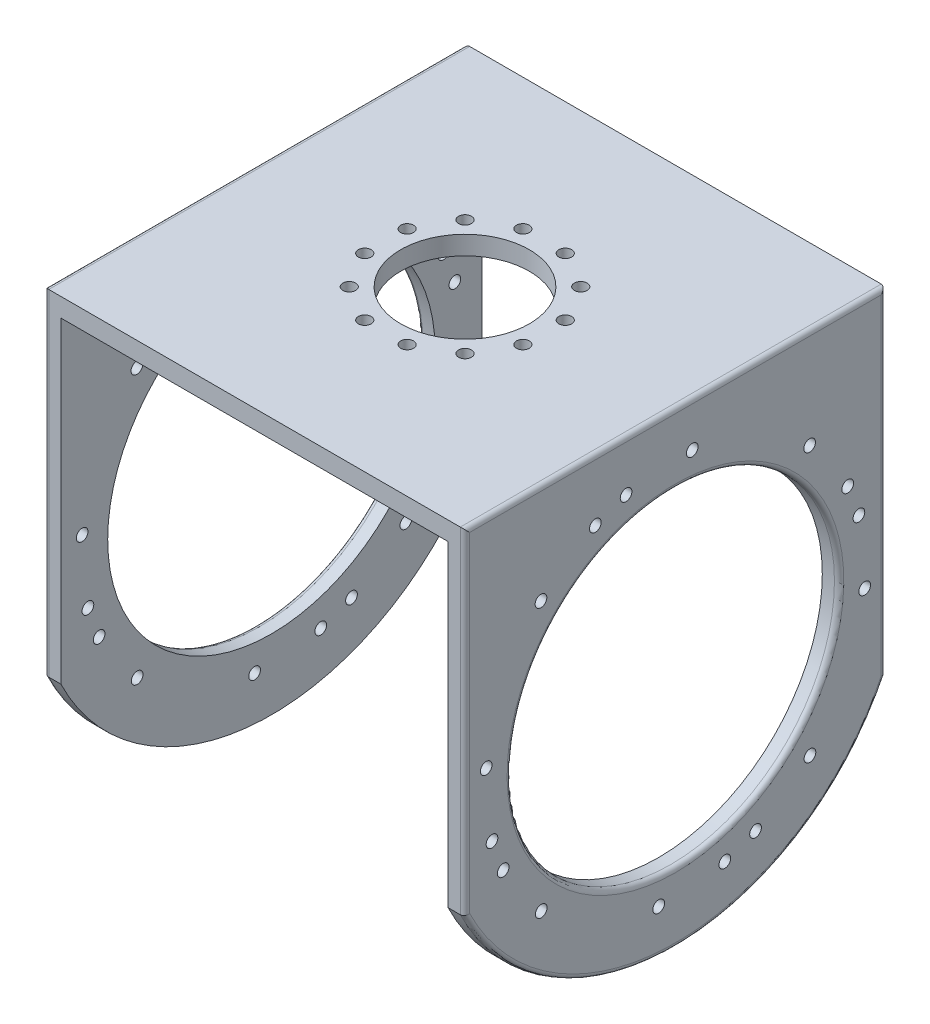
SolidWorks part; units mm, degrees
material "6061 合金"
ref_plane "前视基准面" through (0, 0, 0) normal (0, 0, 1) x (1, 0, 0)
ref_plane "上视基准面" through (0, 0, 0) normal (0, 1, 0) x (1, 0, 0)
ref_plane "右视基准面" through (0, 0, 0) normal (1, 0, 0) x (0, 0, -1)
other "Configuration Table"
sketch "草图1" plane through (0, 0, 0) normal (0, 0, 1) x (1, 0, 0)
  line L0 (0, 0) -> (0, 218.3382) construction
  line L1 (-90, 200) -> (90, 200)
  line L2 (90, 200) -> (90, 0)
  line L3 (90, 0) -> (82.8, 0)
  line L4 (82.8, 0) -> (82.8, 192)
  line L5 (82.8, 192) -> (-82.8, 192)
  line L6 (-82.8, 0) -> (-82.8, 192)
  line L7 (-90, 0) -> (-82.8, 0)
  line L8 (-90, 200) -> (-90, 0)
  point P11 (0, 192)
  point P14 (0, 200)
  dimension "D1" = 8
  dimension "D2" = 7.2
  dimension "D3" = 200
  dimension "D4" = 90
extrude "凸台-拉伸1" add sketch "草图1" along normal blind 180
sketch "草图2" plane through (0, 200, 0) normal (0, 1, 0) x (1, 0, 0)
  line L0 (-107.1953, -90) -> (124.7074, -90) construction
  line L1 (0, 14.5236) -> (0, -191.0225) construction
  line L2 (90, 0) -> (-90, 0) construction
  line L3 (90, -180) -> (-90, -180) construction
  circle A0 centre (0, -90) radius 27.5
  dimension "D1" = 55
extrude "切除-拉伸1" cut sketch "草图2" against normal blind 180
sketch "草图3" plane through (90, 0, 0) normal (1, 0, 0) x (0, 0, -1)
  line L0 (-202.0275, 100) -> (22.0275, 100) construction
  line L1 (-90, 182.9754) -> (-90, -6.0566) construction
  line L2 (-180, 0) -> (0, 0) construction
  line L3 (-180, 200) -> (0, 200) construction
  line L4 (0, 0) -> (0, 200) construction
  line L5 (-180, 0) -> (-180, 200) construction
  circle A0 centre (-90, 100) radius 70
  dimension "D1" = 140
extrude "切除-拉伸2" cut sketch "草图3" against normal blind 217 contours A0
sketch "草图4" plane through (0, 0, 0) normal (1, 0, 0) x (0, 0, -1)
  line L0 (-90, 200) -> (-90, 143.0513) construction
  line L1 (-62.5, 200) -> (-117.5, 200) construction
  line L2 (-70, 430) -> (60, 66.6573)
  line L3 (60, 66.6573) -> (-90, 66.6573) construction
  line L4 (-90, 66.6573) -> (-90, 700) construction
  line L5 (-70, 700) -> (60, 700)
  line L6 (60, 700) -> (60, 66.6573)
  line L7 (-70, 700) -> (-70, 430)
  circle A0 centre (-90, 100) radius 70 construction
  dimension "D1" = 500
  dimension "D2" = 130
  dimension "D3" = 150
  dimension "D4" = 230
  dimension "D5" = 20
revolve "切除-旋转6" [suppressed] cut sketch "草图4" angle 360 about L4
sketch "草图6" [suppressed] plane through (0, 0, 0) normal (1, 0, 0) x (0, 0, -1)
  line L0 (15.1538, 192) -> (60, 66.6573)
  line L1 (-25.1812, 192) -> (0, 192) construction
  line L2 (60, 66.6573) -> (-90, 66.6573) construction
  line L3 (60, 66.6573) -> (51.5034, 66.6573)
  line L4 (51.5034, 66.6573) -> (6.6571, 192)
  line L5 (-70, 430) -> (60, 66.6573) construction
  line L6 (6.6571, 192) -> (15.1538, 192)
  line L7 (-90, 66.6573) -> (-90, 200) construction
  dimension "D1" = 8
revolve "旋转1" [suppressed] add sketch "草图6" angle 360 about L7
sketch "草图7" [suppressed] plane through (0, 0, 0) normal (0, 0, 1) x (1, 0, 0)
  line L0 (90, 0) -> (90, 200)
  line L1 (90, 200) -> (162.5084, 200)
  line L2 (162.5084, 200) -> (162.5084, -21.519)
  line L3 (162.5084, -21.519) -> (-191.6551, -21.519)
  line L4 (-191.6551, -21.519) -> (-191.6551, 200)
  line L5 (-191.6551, 200) -> (-90, 200)
  line L6 (-90, 200) -> (-90, 0)
  line L7 (-90, 0) -> (-82.8, 0)
  line L10 (-35.2505, 192) -> (35.2505, 192)
  line L12 (82.8, 0) -> (90, 0)
  line L14 (35.2505, 192) -> (-35.2505, 192) construction
  line L15 (82.8, 0) -> (82.8, 120.3462)
  line L16 (82.8, 120.3462) -> (35.2505, 192)
  line L17 (-82.8, 0) -> (-82.8, 120.3462)
  line L18 (-82.8, 120.3462) -> (-35.2505, 192)
  line L19 (0, 0) -> (0, 120.3462) construction
  line L21 (35.2505, 192) -> (82.8, 192) construction
  line L22 (-82.8, 0) -> (-82.8, 120.3462) construction
  line L23 (-141.5034, 66.6573) -> (141.5034, 66.6573) construction
  line L24 (-35.2505, 192) -> (35.2505, 192) construction
  dimension "D1" = 53.6889
  dimension "D2" = 35.2505
extrude "切除-拉伸3" [suppressed] cut sketch "草图7" against normal through all both and the other way through all
sketch "草图8" [suppressed] plane through (-90, 0, 0) normal (-1, 0, 0) x (0, 0, 1)
  line L0 (0, 0) -> (0, 200)
  line L1 (0, 200) -> (180, 200)
  line L2 (180, 200) -> (180, 0)
  line L3 (180, 106.4129) -> (180, 0) construction
  line L4 (180, 0) -> (231.7354, 0)
  line L5 (231.7354, 0) -> (231.7354, 213.4055)
  line L6 (231.7354, 213.4055) -> (-43.5189, 213.4055)
  line L7 (-43.5189, 213.4055) -> (-43.5189, 0)
  line L8 (-43.5189, 0) -> (0, 0)
extrude "切除-拉伸4" [suppressed] cut sketch "草图8" against normal through all both
sketch "草图9" plane through (90, 0, 0) normal (1, 0, 0) x (0, 0, -1)
  line L3 (0, 56.411) -> (0, 0)
  line L4 (-180, 200) -> (-180, 0)
  line L5 (-180, 0) -> (0, 0)
  line L6 (0, 0) -> (0, 200)
  line L7 (0, 200) -> (-180, 200)
  line L8 (-180, 56.411) -> (-180, 0)
  line L9 (-180, 0) -> (0, 0)
  line L11 (0, 200) -> (-180, 200) construction
  circle A0 centre (-90, 100) radius 70 construction
  circle A1 centre (-90, 100) radius 70 construction
  arc A3 (-180, 56.411) -> (0, 56.411) centre (-90, 100) ccw
  line M11 (-180, 200) -> (-180, 0)
  line M12 (-180, 0) -> (0, 0)
  line M13 (0, 0) -> (0, 200)
  dimension "D1" = 0
extrude "切除-拉伸5" cut sketch "草图9" against normal through all both contours A3 L9 M13 | A3 M11 M12 region at (90, 15.6044, 21.0435) region at (90, 15.6044, 158.9565)
fillet "圆角1" [suppressed] radius 2
fillet "圆角2" radius 2 10 edges at (90, 200, 90) (90, 128.2055, 0) (90, 0, 90) (90, 128.2055, 180) (90, 170, 90) (-90, 128.2055, 0) (-90, 200, 90) (-90, 128.2055, 180) (-90, 0, 90) (-90, 170, 90)
sketch "草图10" plane through (90, 0, 0) normal (1, 0, 0) x (0, 0, -1)
  arc A0 (-173.1989, 108.2258) -> (-168.6673, 106.1128) centre (-170.9331, 107.1693) ccw construction
  arc A1 (-170.7244, 79.9423) -> (-166.1928, 77.8292) centre (-168.4586, 78.8857) ccw construction
  arc A2 (-165.9405, 66.7988) -> (-161.409, 64.6857) centre (-163.6748, 65.7423) ccw construction
  arc A3 (-149.6558, 43.5418) -> (-145.1242, 41.4287) centre (-147.39, 42.4852) ccw construction
  arc A4 (-99.4351, 20.1235) -> (-94.9035, 18.0104) centre (-97.1693, 19.0669) ccw construction
  arc A5 (-71.1515, 22.598) -> (-66.62, 20.4849) centre (-68.8857, 21.5414) ccw construction
  arc A6 (-58.008, 27.3818) -> (-53.4765, 25.2687) centre (-55.7423, 26.3252) ccw construction
  arc A7 (-34.751, 43.6665) -> (-30.2194, 41.5535) centre (-32.4852, 42.61) ccw construction
  arc A8 (-11.3327, 93.8872) -> (-6.8011, 91.7742) centre (-9.0669, 92.8307) ccw construction
  arc A9 (-13.8072, 122.1708) -> (-9.2756, 120.0577) centre (-11.5414, 121.1143) ccw construction
  arc A10 (-18.591, 135.3143) -> (-14.0595, 133.2012) centre (-16.3252, 134.2577) ccw construction
  arc A11 (-34.8758, 158.5713) -> (-30.3442, 156.4582) centre (-32.61, 157.5148) ccw construction
  arc A12 (-85.0965, 181.9896) -> (-80.5649, 179.8765) centre (-82.8307, 180.9331) ccw construction
  arc A13 (-108.8485, 177.402) -> (-113.38, 179.5151) centre (-111.1143, 178.4586) ccw construction
  arc A14 (-121.992, 172.6182) -> (-126.5235, 174.7313) centre (-124.2577, 173.6748) ccw construction
  arc A15 (-145.249, 156.3335) -> (-149.7806, 158.4465) centre (-147.5148, 157.39) ccw construction
  arc A16 (-173.1989, 108.2258) -> (-168.6673, 106.1128) centre (-170.9331, 107.1693) ccw construction
  arc A17 (-170.7244, 79.9423) -> (-166.1928, 77.8292) centre (-168.4586, 78.8857) ccw construction
  arc A18 (-165.9405, 66.7988) -> (-161.409, 64.6857) centre (-163.6748, 65.7423) ccw construction
  arc A19 (-149.6558, 43.5418) -> (-145.1242, 41.4287) centre (-147.39, 42.4852) ccw construction
  arc A20 (-99.4351, 20.1235) -> (-94.9035, 18.0104) centre (-97.1693, 19.0669) ccw construction
  arc A21 (-71.1515, 22.598) -> (-66.62, 20.4849) centre (-68.8857, 21.5414) ccw construction
  arc A22 (-58.008, 27.3818) -> (-53.4765, 25.2687) centre (-55.7423, 26.3252) ccw construction
  arc A23 (-34.751, 43.6665) -> (-30.2194, 41.5535) centre (-32.4852, 42.61) ccw construction
  arc A24 (-11.3327, 93.8872) -> (-6.8011, 91.7742) centre (-9.0669, 92.8307) ccw construction
  arc A25 (-13.8072, 122.1708) -> (-9.2756, 120.0577) centre (-11.5414, 121.1143) ccw construction
  arc A26 (-18.591, 135.3143) -> (-14.0595, 133.2012) centre (-16.3252, 134.2577) ccw construction
  arc A27 (-34.8758, 158.5713) -> (-30.3442, 156.4582) centre (-32.61, 157.5148) ccw construction
  arc A28 (-85.0965, 181.9896) -> (-80.5649, 179.8765) centre (-82.8307, 180.9331) ccw construction
  arc A29 (-108.8485, 177.402) -> (-113.38, 179.5151) centre (-111.1143, 178.4586) ccw construction
  arc A30 (-121.992, 172.6182) -> (-126.5235, 174.7313) centre (-124.2577, 173.6748) ccw construction
  arc A31 (-145.249, 156.3335) -> (-149.7806, 158.4465) centre (-147.5148, 157.39) ccw construction
  circle A32 centre (-32.61, 157.5148) radius 2.5
  circle A33 centre (-16.3252, 134.2577) radius 2.5
  circle A34 centre (-11.5414, 121.1143) radius 2.5
  circle A35 centre (-9.0669, 92.8307) radius 2.5
  circle A36 centre (-32.4852, 42.61) radius 2.5
  circle A37 centre (-55.7423, 26.3252) radius 2.5
  circle A38 centre (-68.8857, 21.5414) radius 2.5
  circle A39 centre (-97.1693, 19.0669) radius 2.5
  circle A40 centre (-147.39, 42.4852) radius 2.5
  circle A41 centre (-163.6748, 65.7423) radius 2.5
  circle A42 centre (-168.4586, 78.8857) radius 2.5
  circle A43 centre (-170.9331, 107.1693) radius 2.5
  circle A44 centre (-147.5148, 157.39) radius 2.5
  circle A45 centre (-124.2577, 173.6748) radius 2.5
  circle A46 centre (-111.1143, 178.4586) radius 2.5
  circle A47 centre (-82.8307, 180.9331) radius 2.5
  dimension "D1" = 5
extrude "切除-拉伸6" cut sketch "草图10" against normal through all both and the other way through all
sketch "草图11" plane through (0, 192, 0) normal (0, -1, 0) x (1, 0, 0)
  line L0 (0, 90) -> (0, 156.7057) construction
  line L1 (0, 90) -> (16.0765, 149.9982) construction
  circle A0 centre (9.0587, 123.8074) radius 2.75
  circle A1 centre (24.7487, 114.7487) radius 2.75
  circle A2 centre (33.8074, 99.0587) radius 2.75
  circle A3 centre (33.8074, 80.9413) radius 2.75
  circle A4 centre (24.7487, 65.2513) radius 2.75
  circle A5 centre (9.0587, 56.1926) radius 2.75
  circle A6 centre (-9.0587, 56.1926) radius 2.75
  circle A7 centre (-24.7487, 65.2513) radius 2.75
  circle A8 centre (-33.8074, 80.9413) radius 2.75
  circle A9 centre (-33.8074, 99.0587) radius 2.75
  circle A10 centre (-24.7487, 114.7487) radius 2.75
  circle A11 centre (-9.0587, 123.8074) radius 2.75
  point P31 (0, 90)
  dimension "D1" = 5.5
  dimension "D2" = 35
  dimension "D3" = 15
  dimension "D4" = 12
extrude "切除-拉伸7" cut sketch "草图11" against normal blind 29
